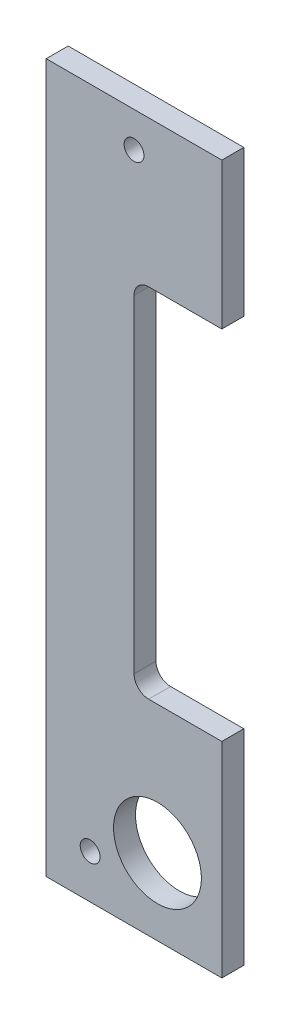
SolidWorks part; units mm, degrees
ref_plane "Front Plane" through (0, 0, 0) normal (0, 0, 1) x (1, 0, 0)
ref_plane "Top Plane" through (0, 0, 0) normal (0, 1, 0) x (1, 0, 0)
ref_plane "Right Plane" through (0, 0, 0) normal (1, 0, 0) x (0, 0, -1)
sketch "Sketch1" plane through (0, 0, 0) normal (0, 0, 1) x (1, 0, 0)
  line L8 (0, 44.45) -> (-15.875, 44.45)
  line L9 (-19.05, 47.625) -> (-19.05, 118.745)
  line L10 (-15.875, 121.92) -> (0, 121.92)
  line L11 (0, 121.92) -> (0, 153.67)
  line L12 (0, 153.67) -> (-38.1, 153.67)
  line L13 (-38.1, 153.67) -> (-38.1, 0)
  line L14 (-38.1, 0) -> (0, 0)
  line L15 (0, 0) -> (0, 44.45)
  line L16 (0, 44.45) -> (-15.875, 44.45)
  line L17 (-19.05, 47.625) -> (-19.05, 118.745)
  line L18 (-15.875, 121.92) -> (0, 121.92)
  line L19 (0, 121.92) -> (0, 153.67)
  line L20 (0, 153.67) -> (-38.1, 153.67)
  line L21 (-38.1, 153.67) -> (-38.1, 0)
  line L22 (-38.1, 0) -> (0, 0)
  line L23 (0, 0) -> (0, 44.45)
  arc A2 (-19.05, 47.625) -> (-15.875, 44.45) centre (-15.875, 47.625) ccw
  arc A3 (-15.875, 121.92) -> (-19.05, 118.745) centre (-15.875, 118.745) ccw
  arc A4 (-19.05, 47.625) -> (-15.875, 44.45) centre (-15.875, 47.625) ccw
  arc A5 (-15.875, 121.92) -> (-19.05, 118.745) centre (-15.875, 118.745) ccw
  dimension "D1" = 0
extrude "Boss-Extrude1" add sketch "Sketch1" against normal blind 4.7625
hole_wizard "#6 Clearance Hole1" positions "Sketch3" profile "Sketch2" hole size "#6" standard "ANSI Inch" end condition through all
sketch "Sketch3" plane through (0, 0, -4.7625) normal (0, 0, -1) x (-1, 0, 0)
  point P0 (28.575, 9.525)
  point P3 (19.05, 146.05)
sketch "Sketch2" plane through (-28.575, 9.525, -4.7625) normal (1, 0, 0) x (0, 1, 0)
  line L0 (0, 0) -> (0, 4.7625)
  line L1 (0, 4.7625) -> (2.1526, 4.7625)
  line L2 (2.1526, 4.7625) -> (2.1526, 0)
  line L5 (2.1526, 0) -> (0, 0)
  line L11 (0, -6.35) -> (0, 107.95) construction
  dimension "Thru Hole Dia." = 4.3053
  dimension "Thru Hole Depth" = 4.7625
hole_wizard "3/4 (0.75) Diameter Hole1" positions "Sketch5" profile "Sketch4" hole size "3/4" standard "ANSI Inch" end condition through all
sketch "Sketch5" plane through (0, 0, -4.7625) normal (0, 0, -1) x (-1, 0, 0)
  point P0 (13.97, 16.51)
sketch "Sketch4" plane through (-13.97, 16.51, -4.7625) normal (1, 0, 0) x (0, 1, 0)
  line L0 (0, 0) -> (0, 4.7625)
  line L1 (0, 4.7625) -> (9.525, 4.7625)
  line L2 (9.525, 4.7625) -> (9.525, 0)
  line L5 (9.525, 0) -> (0, 0)
  line L11 (0, -6.35) -> (0, 107.95) construction
  dimension "Thru Hole Dia." = 19.05
  dimension "Thru Hole Depth" = 4.7625
